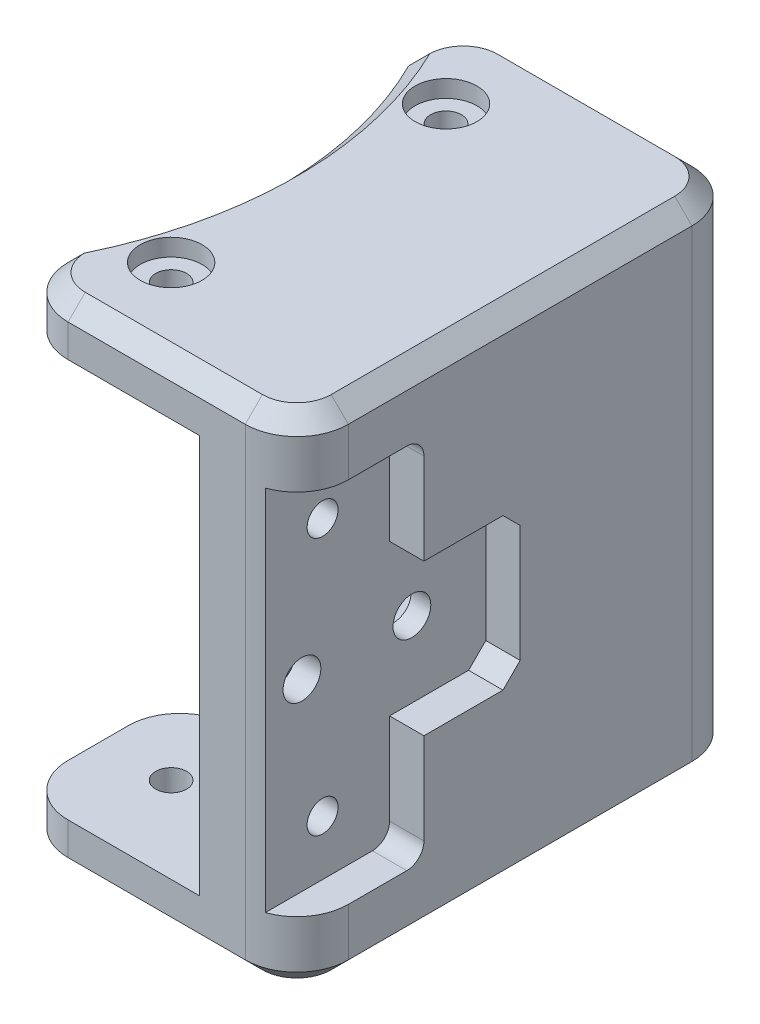
SolidWorks part; units mm, degrees
ref_plane "Спереди" through (0, 0, 0) normal (0, 0, 1) x (1, 0, 0)
ref_plane "Сверху" through (0, 0, 0) normal (0, 1, 0) x (1, 0, 0)
ref_plane "Справа" through (0, 0, 0) normal (1, 0, 0) x (0, 0, -1)
sketch "Эскиз1" plane through (0, 0, 0) normal (0, 1, 0) x (1, 0, 0)
  line L0 (0, 0) -> (25, 0) construction
  line L1 (19.6854, 13) -> (36, 13)
  line L2 (19.6854, 13) -> (19.6854, -13)
  line L3 (19.6854, -13) -> (36, -13)
  line L4 (36, 13) -> (36, -13)
  line L5 (19.6854, 13) -> (36, -13) construction
  line L6 (19.6854, -13) -> (36, 13) construction
  line L7 (23.6854, 8) -> (23.6854, -8) construction
  circle A0 centre (0, 0) radius 25 construction
  circle A1 centre (23.6854, -8) radius 0.9
  circle A2 centre (23.6854, 8) radius 0.9
  point P0 (27.8427, 0)
  dimension "D2" = 50
  dimension "D6" = 1.8
  dimension "D7" = 1.8
  dimension "D1" = 36
  dimension "D3" = 26
  dimension "D4" = 16
  dimension "D5" = 4
extrude "Бобышка-Вытянуть1" add sketch "Эскиз1" along normal mid plane 29
sketch "Эскиз2" plane through (0, 0, 0) normal (0, 1, 0) x (1, 0, 0)
  circle A0 centre (0, 0) radius 33
  dimension "D1" = 66
extrude "Вырез-Вытянуть1" cut sketch "Эскиз2" against normal mid plane 23.2
sketch "Эскиз3" plane through (36, 0, 0) normal (1, 0, 0) x (0, 0, -1)
  line L0 (-13, 10.7) -> (-5.6, 10.7)
  line L1 (-13, 14.5) -> (-13, -14.5) construction
  line L2 (-5.6, 10.7) -> (-5.6, 4.4)
  line L3 (-5.6, 4.4) -> (0, 4.4)
  line L4 (0, 4.4) -> (0, -4.4)
  line L5 (-13, 10.7) -> (-13, -10.7)
  line L6 (0, 0) -> (-13, 0) construction
  line L7 (-5.6, -4.4) -> (0, -4.4)
  line L8 (-5.6, -10.7) -> (-5.6, -4.4)
  line L9 (-13, -10.7) -> (-5.6, -10.7)
  dimension "D1" = 7.4
  dimension "D2" = 13
  dimension "D3" = 21.4
  dimension "D4" = 8.8
extrude "Вырез-Вытянуть2" cut sketch "Эскиз3" against normal blind 2
sketch "Эскиз8" plane through (0, 14.5, 0) normal (0, 1, 0) x (1, 0, 0)
  circle A0 centre (0, 0) radius 22
  dimension "D1" = 44
extrude "Вырез-Вытянуть7" cut sketch "Эскиз8" against normal up to next
fillet "Скругление1" radius 1 2 edges at (35, -10.7, 5.6) (35, 10.7, 5.6)
chamfer "Фаска1" distance 1 angle 45 2 edges at (35, -4.4, 0) (35, 4.4, 0)
sketch "Эскиз4" plane through (34, 0, 0) normal (1, 0, 0) x (0, 0, -1)
  line L0 (-13, 10.7) -> (-13, -10.7) construction
  circle A0 centre (-4.3, 0) radius 1.1
  circle A1 centre (-10.7, 0) radius 1.1
  dimension "D1" = 2.2
  dimension "D2" = 2.2
  dimension "D3" = 8.7
  dimension "D4" = 6.4
extrude "Вырез-Вытянуть3" cut sketch "Эскиз4" against normal blind 1.5
sketch "Эскиз5" plane through (34, 0, 0) normal (1, 0, 0) x (0, 0, -1)
  line L0 (-13, 0) -> (0, 0) construction
  line L1 (-13, 10.7) -> (-13, -10.7) construction
  circle A0 centre (-9.5, 7.5) radius 0.9
  circle A1 centre (-9.5, -7.5) radius 0.9
  dimension "D3" = 1.8
  dimension "D1" = 3.5
  dimension "D2" = 15
extrude "Вырез-Вытянуть4" cut sketch "Эскиз5" against normal through all
sketch "Эскиз6" plane through (0, -14.5, 0) normal (0, -1, 0) x (1, 0, 0)
  line L0 (19.6854, -13) -> (19.6854, 13) construction
  line L1 (25, 3.5) -> (19.6854, 3.5)
  line L2 (25, 3.5) -> (25, -3.5)
  line L3 (25, -3.5) -> (19.6854, -3.5)
  line L4 (19.6854, 3.5) -> (19.6854, -3.5)
  circle A0 centre (0, 0) radius 25 construction
  circle A1 centre (25, 0) radius 3.5
  line M7 (19.6854, 13) -> (19.6854, -13)
  dimension "D1" = 50
  dimension "D2" = 7
extrude "Вырез-Вытянуть5" cut sketch "Эскиз6" against normal up to next contours A1 L1 L3 M7 | L2 A1 | L2 A1 region at (21.0872, -14.5, 0) region at (26.4854, -14.5, 0) region at (23.5146, -14.5, 0)
fillet "Скругление2" radius 3 8 edges at (19.6854, 13.05, -13) (19.6854, 13.05, 13) (19.6854, -13.05, -13) (19.6854, -13.05, 13) (36, 0, -13) (36, 12.6, 13) (19.6854, -13.05, 3.5) (19.6854, -13.05, -3.5)
chamfer "Фаска3" distance 1 angle 45 22 edges at (23.8427, -14.5, 3.5) (28.5, -14.5, 0) (20.5641, -14.5, 4.3787) (23.8427, -14.5, -3.5) (19.6854, -14.5, 8.25) (20.5641, -14.5, -4.3787) (20.5641, -14.5, 12.1213) (19.6854, -14.5, -8.25) (27.8427, -14.5, 13) (20.5641, -14.5, -12.1213) (35.1213, -14.5, 12.1213) (27.8427, -14.5, -13) (36, -14.5, 0) (35.1213, -14.5, -12.1213) (27.8427, 14.5, 13) (35.1213, 14.5, 12.1213) (20.5641, 14.5, 12.1213) (36, 14.5, 0) (35.1213, 14.5, -12.1213) (20.5641, 14.5, -12.1213) (27.8427, 14.5, -13) (19.6854, 14.5, 9.9113)
sketch "Эскиз7" plane through (0, 14.5, 0) normal (0, 1, 0) x (1, 0, 0)
  circle A0 centre (23.6854, 8) radius 1.8
  circle A1 centre (23.6854, -8) radius 1.8
  dimension "D1" = 3.6
  dimension "D2" = 3.6
extrude "Вырез-Вытянуть6" cut sketch "Эскиз7" against normal blind 1
mirror "Зеркальное отражение1" about plane through (0, 0, 0) normal (0, 1, 0) of "Вырез-Вытянуть6"
chamfer "Фаска4" distance 1 angle 45 1 edges at (22, 14.5, 0)
equation "\"motor_diameter\"= 30"
equation "\"mm_diameter\"= IIF ( \"motor_diameter\" < 34 , 41 , \"motor_diameter\" + 8 )"
equation "\"upper_shafts_diameter\"= 5"
equation "\"upper_shats_length\"= 180"
equation "\"upper_bearing_d1\"= 10"
equation "\"upper_bearing_d2\"= 5"
equation "\"upper_bearing_h\"= 15"
equation "\"lower_shafts_diameter\"= 5"
equation "\"lower_shafts_length\"= 180"
equation "\"lower_bearing_d1\"= 10"
equation "\"lower_bearing_d2\"= 5"
equation "\"lower_bearing_h\"= 15"
equation "\"print_offset\"= 0.2"
equation "\"bh_screws_d\"= 2"
equation "\"bh_screws_h\"= 20"
equation "\"bh_screws_hh_d\"= 3.4"
equation "\"bh_screws_hh_h\"= 2"
equation "\"bh_nut_d\"= 3.8"
equation "\"bh_nut_h\"= 2"
equation "\"motor_screws_d\"= 3"
equation "\"motor_screws_h\"= 16"
equation "\"motor_screws_hh_d\"= 5.5"
equation "\"motor_screws_hh_h\"= 3"
equation "\"plate_hole_distance\"= 25.4"
equation "\"plate_screws_d\"= 6.5"
equation "\"shafts_diameter\"= IIF ( \"mm_diameter\" < 42 , 42 + 8 , \"mm_diameter\" + 8 )"
equation "\"central_hole_diameter\"= 8"
equation "\"bh_thikness\"= 4"
equation "\"ends_screws_d\"= 4"
equation "\"ends_screws_h\"= 16"
equation "\"ends_screws_hh_d\"= 6.7"
equation "\"ends_screws_hh_h\"= 4.1"
equation "\"ends_nut_d\"= 6.8"
equation "\"ends_nut_h\"= 3"
equation "\"system_radius\" = ( \"shafts_diameter\" + 12 + \"bh_thikness\" / 2 ) / 2"
equation "\"encoder_distance\"= \"system_radius\" + 4"
equation "\"tape_position\"= \"encoder_distance\" - 2 + 3.9 + 1.7 / 2"
equation "\"D1@Эскиз1\"=\"encoder_distance\""
equation "\"D2@Эскиз1\"=\"shafts_diameter\""
equation "\"D5@Эскиз1\"=\"bh_thikness\""
equation "\"D6@Эскиз1\"=\"bh_screws_d\"-\"print_offset\""
equation "\"D7@Эскиз1\"=\"D6@Эскиз1\""
equation "\"D1@Бобышка-Вытянуть1\"=\"upper_bearing_h\"+\"bh_thikness\"*2+3*2"
equation "\"D1@Эскиз2\"=\"system_radius\"*2+2"
equation "\"D1@Вырез-Вытянуть1\"=\"upper_bearing_h\"+\"bh_thikness\"*2+\"print_offset\""
equation "\"D1@Эскиз3\"=\"print_offset\"*2+7"
equation "\"D2@Эскиз3\"=\"print_offset\"*2+12.6"
equation "\"D3@Эскиз3\"=\"print_offset\"*2+21"
equation "\"D4@Эскиз3\"=\"print_offset\"*2+8.4"
equation "\"D2@Эскиз4\"=\"print_offset\"+2"
equation "\"D1@Эскиз4\"=\"D2@Эскиз4\""
equation "\"D1@Эскиз5\"=7/2"
equation "\"D3@Эскиз5\"=\"bh_screws_d\"-\"print_offset\""
equation "\"D1@Эскиз6\"=\"shafts_diameter\""
equation "\"D2@Эскиз6\"=\"lower_shafts_diameter\"+2"
equation "\"D1@Эскиз7\"=\"bh_screws_hh_d\"+\"print_offset\""
equation "\"D2@Эскиз7\"=\"D1@Эскиз7\""
equation "\"D1@Эскиз8\"= IIF ( \"mm_diameter\" < 42 , 44 , \"mm_diameter\" + 2 )"
